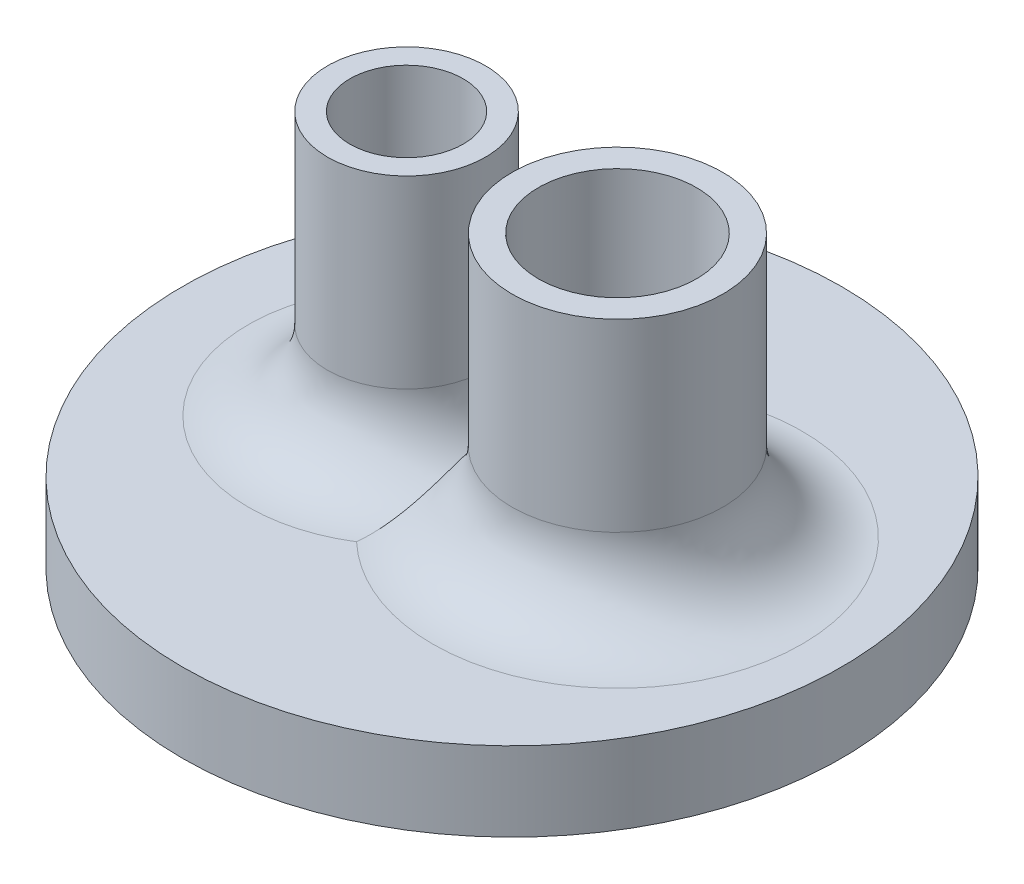
SolidWorks part; units mm, degrees
ref_plane "Front Plane" through (0, 0, 0) normal (0, 0, 1) x (1, 0, 0)
ref_plane "Top Plane" through (0, 0, 0) normal (0, 1, 0) x (1, 0, 0)
ref_plane "Right Plane" through (0, 0, 0) normal (1, 0, 0) x (0, 0, -1)
sketch "Sketch1" plane through (0, 0, 0) normal (0, 1, 0) x (1, 0, 0)
  circle A0 centre (0, 0) radius 12.5
  dimension "D1" = 25
extrude "Boss-Extrude1" add sketch "Sketch1" along normal blind 3 contours A0
sketch "Sketch2" plane through (0, 3, 0) normal (0, 1, 0) x (1, 0, 0)
  circle A0 centre (4, 0) radius 4
  circle A1 centre (-4, 0) radius 3
  dimension "D1" = 6
  dimension "D2" = 8
  dimension "D3" = 4
  dimension "D4" = 4
extrude "Boss-Extrude2" add sketch "Sketch2" along normal blind 10
sketch "Sketch3" plane through (0, 13, 0) normal (0, 1, 0) x (1, 0, 0)
  circle A0 centre (-4, 0) radius 2.15
  circle A1 centre (4, 0) radius 3
  dimension "D1" = 4.3
  dimension "D2" = 6
extrude "Cut-Extrude1" cut sketch "Sketch3" against normal through all
fillet "Fillet1" radius 3 2 edges at (4, 3, 4) (-4, 3, 3)
